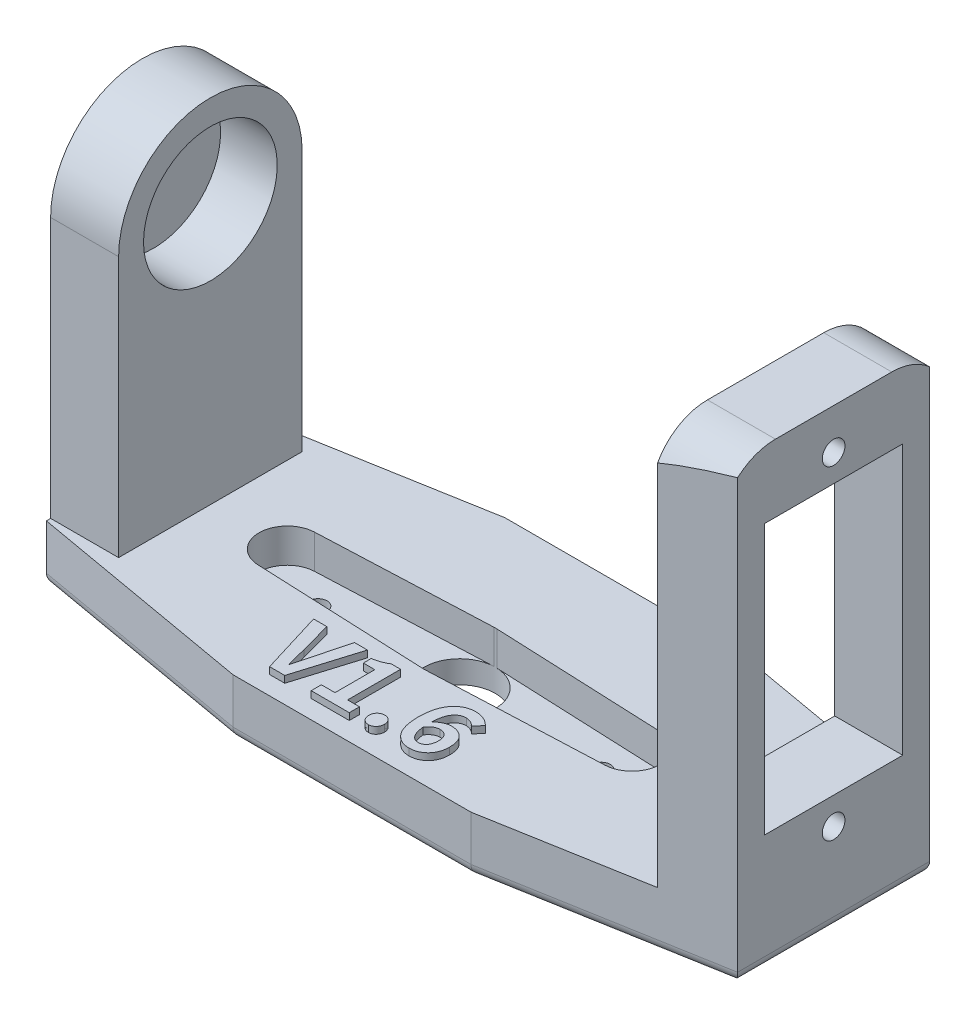
SolidWorks part; units mm, degrees
ref_plane "前视基准面" through (0, 0, 0) normal (0, 0, 1) x (1, 0, 0)
ref_plane "上视基准面" through (0, 0, 0) normal (0, 1, 0) x (1, 0, 0)
ref_plane "右视基准面" through (0, 0, 0) normal (1, 0, 0) x (0, 0, -1)
sketch "草图1" plane through (0, 0, 0) normal (0, 1, 0) x (1, 0, 0)
  line L0 (0, 0) -> (2.5, 0) construction
  line L1 (33, -12) -> (-28, -12)
  line L2 (33, -12) -> (33, 12)
  line L3 (33, 12) -> (-28, 12)
  line L4 (-28, -12) -> (-28, 12)
  line L5 (33, -12) -> (-28, 12) construction
  line L6 (33, 12) -> (-28, -12) construction
  point P0 (0, 0)
  dimension "D1" = 28
  dimension "D2" = 33
  dimension "D3" = 24
extrude "凸台-拉伸1" add sketch "草图1" along normal blind 5
sketch "草图2" plane through (-28, 0, 0) normal (-1, 0, 0) x (0, 0, 1)
  line L0 (-12, 5) -> (12, 5) construction
  line L1 (8.0991, 36.0991) -> (-8.0991, 36.0991)
  line L2 (8.0991, 36.0991) -> (8.0991, 5)
  line L3 (8.0991, 5) -> (-8.0991, 5)
  line L4 (-8.0991, 36.0991) -> (-8.0991, 5)
  line L5 (8.0991, 36.0991) -> (-8.0991, 5) construction
  line L6 (8.0991, 5) -> (-8.0991, 36.0991) construction
  line L7 (0, 20.5496) -> (0, 5) construction
  circle A0 centre (0, 28) radius 5.9
  circle A1 centre (0, 28) radius 8.0991 construction
  point P0 (0, 20.5496)
  dimension "D2" = 11.8
  dimension "D1" = 23
extrude "凸台-拉伸2" add sketch "草图2" against normal blind 6
sketch "草图8" plane through (-28, 0, 0) normal (-1, 0, 0) x (0, 0, 1)
  circle A1 centre (0, 28) radius 5.9 construction
  circle A2 centre (0, 28) radius 5.9
extrude "凸台-拉伸4" add sketch "草图8" against normal blind 1
fillet "圆角1" 2 edges at (-25, 36.0991, -8.0991) (-25, 36.0991, 8.0991) type full round first side face at (-25, 20.5496, -8.0991) second side face at (-25, 20.5496, 8.0991) middle face at (-25, 36.0991, 0)
sketch "草图3" plane through (33, 0, 0) normal (1, 0, 0) x (0, 0, -1)
  line L0 (0, 22.2) -> (18.2252, 22.2) construction
  line L1 (10.134, 40.0752) -> (-10.134, 40.0752)
  line L2 (10.134, 40.0752) -> (10.134, 5)
  line L3 (10.134, 5) -> (-10.134, 5)
  line L4 (-10.134, 40.0752) -> (-10.134, 5)
  line L5 (10.134, 40.0752) -> (-10.134, 5) construction
  line L6 (10.134, 5) -> (-10.134, 40.0752) construction
  line L7 (0, 22.2) -> (0, 0) construction
  line L8 (6.1, 34.1) -> (-6.1, 34.1)
  line L9 (6.1, 34.1) -> (6.1, 10.3)
  line L10 (6.1, 10.3) -> (-6.1, 10.3)
  line L11 (-6.1, 34.1) -> (-6.1, 10.3)
  line L12 (6.1, 34.1) -> (-6.1, 10.3) construction
  line L13 (6.1, 10.3) -> (-6.1, 34.1) construction
  line L17 (-12, 5) -> (12, 5) construction
  circle A0 centre (0, 28) radius 5.9 construction
  circle A1 centre (0, 28) radius 5.9 construction
  circle A2 centre (0, 7.9) radius 1
  circle A3 centre (0, 36.5) radius 1
  circle A4 centre (0, 28) radius 6.1 construction
  point P0 (0, 22.5376)
  point P7 (0, 22.2)
  dimension "D5" = 2
  dimension "D1" = 23.8
  dimension "D2" = 12.2
  dimension "D4" = 14.3
extrude "凸台-拉伸3" add sketch "草图3" against normal blind 6
fillet "圆角2" radius 5 2 edges at (30, 40.0752, 10.134) (30, 40.0752, -10.134)
chamfer "倒角1" distance 20 angle 10 4 edges at (33, 2.5, -12) (33, 2.5, 12) (-28, 2.5, 12) (-28, 2.5, -12) first distance on face at (2.5, 2.5, -12) first distance on face at (2.5, 2.5, 12)
fillet "圆角4" radius 1 8 edges at (-18, 0, -10.2367) (-28, 0, 0) (-18, 0, 10.2367) (2.5, 0, 12) (23, 0, 10.2367) (33, 0, 0) (23, 0, -10.2367) (2.5, 0, -12)
sketch "草图4" plane through (-24, 5, 6) normal (0, -1, 0) x (-1, 0, 0)
  line L0 (-24, 6) -> (-8.7944, 6) construction
  line L1 (-8.6961, 3.7021) -> (-23.8739, 3.0527) construction
  line L2 (-23.8739, 8.9473) -> (-8.6961, 8.2979) construction
  line L3 (-23.8653, 9.1471) -> (-8.6876, 8.4977)
  line L4 (-8.6876, 3.5023) -> (-23.8653, 2.8529)
  arc A0 (-23.8739, 8.9473) -> (-23.8739, 3.0527) centre (-24, 6) ccw construction
  arc A1 (-8.6961, 3.7021) -> (-8.6961, 8.2979) centre (-8.7944, 6) ccw construction
  arc A2 (-8.6876, 3.5023) -> (-8.6876, 8.4977) centre (-8.7944, 6) ccw
  arc A3 (-23.8653, 9.1471) -> (-23.8653, 2.8529) centre (-24, 6) ccw
  dimension "D1" = 5.9
  dimension "D2" = 4.6
  dimension "D3" = 4.9
  dimension "D5" = 0.2
extrude "切除-拉伸1" cut sketch "草图4" along normal blind 3
mirror "镜向1" about plane through (0, 0, 0) normal (1, 0, 0) of "切除-拉伸1"
sketch "草图5" plane through (0, 2, 0) normal (0, 1, 0) x (1, 0, 0)
  line L0 (-12.5, 0) -> (0, 0) construction
  line L1 (0, 0) -> (0, 5.837) construction
  arc A1 (-0.1347, -3.1471) -> (0.1347, -3.1471) centre (0, 0) ccw construction
  arc A2 (0.1347, 3.1471) -> (-0.1347, 3.1471) centre (0, 0) ccw construction
  arc A3 (-0.1347, -3.1471) -> (0.1347, -3.1471) centre (0, 0) ccw construction
  arc A4 (0.1347, 3.1471) -> (-0.1347, 3.1471) centre (0, 0) ccw construction
  circle A5 centre (0, 0) radius 3.15
  circle A6 centre (-12.5, 0) radius 0.8
  circle A7 centre (12.5, 0) radius 0.8
  dimension "D2" = 1.6
  dimension "D1" = 12.5
extrude "切除-拉伸2" cut sketch "草图5" against normal blind 2.4
sketch "草图10" plane through (0, 5, 0) normal (0, 1, 0) x (1, 0, 0)
  line L0 (-11.9016, -10.3725) -> (11.9016, -10.3725) construction
  line L1 (0, 0) -> (0, -10.3725) construction
  text T0 "V1.6" font "思源黑体" height in points 18
extrude "凸台-拉伸5" add sketch "草图10" along normal blind 0.6
